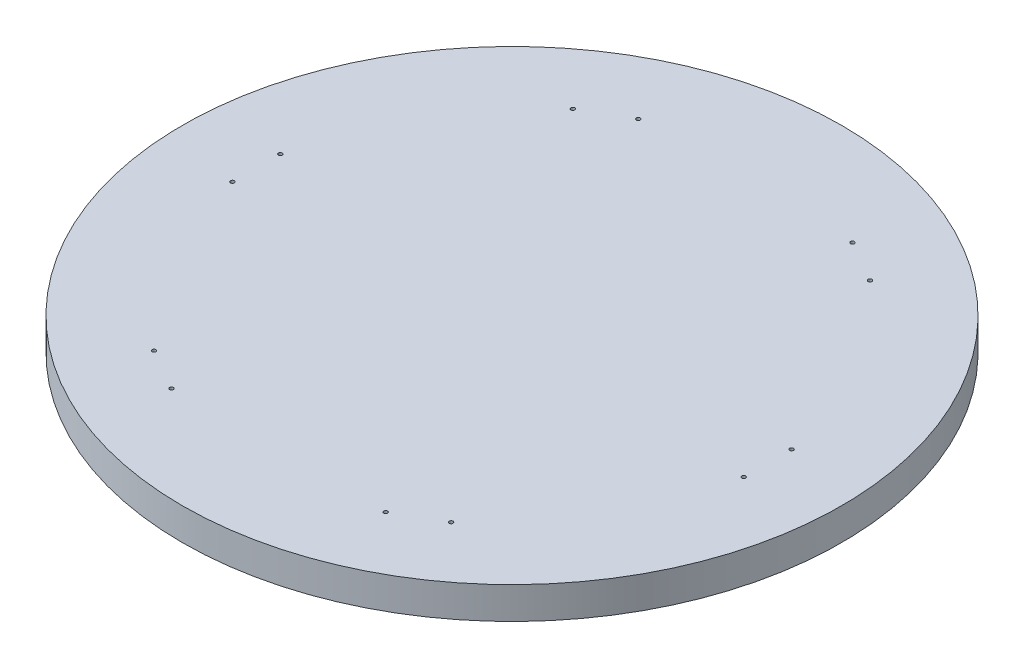
SolidWorks part; units mm, degrees
ref_plane "Front Plane" through (0, 0, 0) normal (0, 0, 1) x (1, 0, 0)
ref_plane "Top Plane" through (0, 0, 0) normal (0, 1, 0) x (1, 0, 0)
ref_plane "Right Plane" through (0, 0, 0) normal (1, 0, 0) x (0, 0, -1)
sketch "Sketch1" plane through (0, 0, 0) normal (0, 1, 0) x (1, 0, 0)
  circle A0 centre (0, 0) radius 261.9375
extrude "Boss-Extrude1" add sketch "Sketch1" along normal blind 25.4
sketch "Sketch6" plane through (0, 0, 0) normal (0, -1, 0) x (1, 0, 0)
  line L0 (203.2, 19.05) -> (203.2, -19.05) construction
  line L1 (215.9, 19.05) -> (215.9, -19.05)
  line L2 (190.5, 19.05) -> (190.5, -19.05)
  line L3 (203.2, -16.5451) -> (201.0307, -17.7976) construction
  line L4 (201.0307, -17.7976) -> (201.0307, -20.3024) construction
  line L5 (201.0307, -20.3024) -> (203.2, -21.5549) construction
  line L6 (203.2, -21.5549) -> (205.3693, -20.3024) construction
  line L7 (205.3693, -20.3024) -> (205.3693, -17.7976) construction
  line L8 (205.3693, -17.7976) -> (203.2, -16.5451) construction
  line L9 (203.2, 22.1294) -> (201.0307, 20.8769) construction
  line L10 (201.0307, 20.8769) -> (201.0307, 18.372) construction
  line L11 (201.0307, 18.372) -> (203.2, 17.1196) construction
  line L12 (203.2, 17.1196) -> (205.3693, 18.372) construction
  line L13 (205.3693, 18.372) -> (205.3693, 20.8769) construction
  line L14 (205.3693, 20.8769) -> (203.2, 22.1294) construction
  line L15 (0, 0) -> (203.2, 0) construction
  line L16 (87.2715, -184.2489) -> (85.1022, -182.9965) construction
  line L17 (85.1022, -182.9965) -> (82.9329, -184.2489) construction
  line L18 (82.9329, -184.2489) -> (82.9329, -186.7538) construction
  line L19 (82.9329, -186.7538) -> (85.1022, -188.0063) construction
  line L20 (85.1022, -188.0063) -> (87.2715, -186.7538) construction
  line L21 (87.2715, -186.7538) -> (87.2715, -184.2489) construction
  line L22 (120.7646, -164.9117) -> (118.5953, -163.6592) construction
  line L23 (118.5953, -163.6592) -> (116.426, -164.9117) construction
  line L24 (116.426, -164.9117) -> (116.426, -167.4166) construction
  line L25 (116.426, -167.4166) -> (118.5953, -168.669) construction
  line L26 (118.5953, -168.669) -> (120.7646, -167.4166) construction
  line L27 (120.7646, -167.4166) -> (120.7646, -164.9117) construction
  line L28 (0, 0) -> (101.6, -175.9764) construction
  line L29 (118.0978, -166.4514) -> (85.1022, -185.5014) construction
  line L30 (124.4478, -177.4499) -> (91.4522, -196.4999)
  line L31 (111.7478, -155.4528) -> (78.7522, -174.5028)
  line L32 (-115.9285, -167.7038) -> (-115.9285, -165.1989) construction
  line L33 (-115.9285, -165.1989) -> (-118.0978, -163.9465) construction
  line L34 (-118.0978, -163.9465) -> (-120.2671, -165.1989) construction
  line L35 (-120.2671, -165.1989) -> (-120.2671, -167.7038) construction
  line L36 (-120.2671, -167.7038) -> (-118.0978, -168.9563) construction
  line L37 (-118.0978, -168.9563) -> (-115.9285, -167.7038) construction
  line L38 (-82.4354, -187.0411) -> (-82.4354, -184.5362) construction
  line L39 (-82.4354, -184.5362) -> (-84.6047, -183.2837) construction
  line L40 (-84.6047, -183.2837) -> (-86.774, -184.5362) construction
  line L41 (-86.774, -184.5362) -> (-86.774, -187.0411) construction
  line L42 (-86.774, -187.0411) -> (-84.6047, -188.2935) construction
  line L43 (-84.6047, -188.2935) -> (-82.4354, -187.0411) construction
  line L44 (0, 0) -> (-101.6, -175.9764) construction
  line L45 (-85.1022, -185.5014) -> (-118.0978, -166.4514) construction
  line L46 (-91.4522, -196.4999) -> (-124.4478, -177.4499)
  line L47 (-78.7522, -174.5028) -> (-111.7478, -155.4528)
  line L48 (-203.2, 16.5451) -> (-201.0307, 17.7976) construction
  line L49 (-201.0307, 17.7976) -> (-201.0307, 20.3024) construction
  line L50 (-201.0307, 20.3024) -> (-203.2, 21.5549) construction
  line L51 (-203.2, 21.5549) -> (-205.3693, 20.3024) construction
  line L52 (-205.3693, 20.3024) -> (-205.3693, 17.7976) construction
  line L53 (-205.3693, 17.7976) -> (-203.2, 16.5451) construction
  line L54 (-203.2, -22.1294) -> (-201.0307, -20.8769) construction
  line L55 (-201.0307, -20.8769) -> (-201.0307, -18.372) construction
  line L56 (-201.0307, -18.372) -> (-203.2, -17.1196) construction
  line L57 (-203.2, -17.1196) -> (-205.3693, -18.372) construction
  line L58 (-205.3693, -18.372) -> (-205.3693, -20.8769) construction
  line L59 (-205.3693, -20.8769) -> (-203.2, -22.1294) construction
  line L60 (0, 0) -> (-203.2, 0) construction
  line L61 (-203.2, -19.05) -> (-203.2, 19.05) construction
  line L62 (-215.9, -19.05) -> (-215.9, 19.05)
  line L63 (-190.5, -19.05) -> (-190.5, 19.05)
  line L64 (-87.2715, 184.2489) -> (-85.1022, 182.9965) construction
  line L65 (-85.1022, 182.9965) -> (-82.9329, 184.2489) construction
  line L66 (-82.9329, 184.2489) -> (-82.9329, 186.7538) construction
  line L67 (-82.9329, 186.7538) -> (-85.1022, 188.0063) construction
  line L68 (-85.1022, 188.0063) -> (-87.2715, 186.7538) construction
  line L69 (-87.2715, 186.7538) -> (-87.2715, 184.2489) construction
  line L70 (-120.7646, 164.9117) -> (-118.5953, 163.6592) construction
  line L71 (-118.5953, 163.6592) -> (-116.426, 164.9117) construction
  line L72 (-116.426, 164.9117) -> (-116.426, 167.4166) construction
  line L73 (-116.426, 167.4166) -> (-118.5953, 168.669) construction
  line L74 (-118.5953, 168.669) -> (-120.7646, 167.4166) construction
  line L75 (-120.7646, 167.4166) -> (-120.7646, 164.9117) construction
  line L76 (0, 0) -> (-101.6, 175.9764) construction
  line L77 (-118.0978, 166.4514) -> (-85.1022, 185.5014) construction
  line L78 (-124.4478, 177.4499) -> (-91.4522, 196.4999)
  line L79 (-111.7478, 155.4528) -> (-78.7522, 174.5028)
  line L80 (115.9285, 167.7038) -> (115.9285, 165.1989) construction
  line L81 (115.9285, 165.1989) -> (118.0978, 163.9465) construction
  line L82 (118.0978, 163.9465) -> (120.2671, 165.1989) construction
  line L83 (120.2671, 165.1989) -> (120.2671, 167.7038) construction
  line L84 (120.2671, 167.7038) -> (118.0978, 168.9563) construction
  line L85 (118.0978, 168.9563) -> (115.9285, 167.7038) construction
  line L86 (82.4354, 187.0411) -> (82.4354, 184.5362) construction
  line L87 (82.4354, 184.5362) -> (84.6047, 183.2837) construction
  line L88 (84.6047, 183.2837) -> (86.774, 184.5362) construction
  line L89 (86.774, 184.5362) -> (86.774, 187.0411) construction
  line L90 (86.774, 187.0411) -> (84.6047, 188.2935) construction
  line L91 (84.6047, 188.2935) -> (82.4354, 187.0411) construction
  line L92 (0, 0) -> (101.6, 175.9764) construction
  line L93 (85.1022, 185.5014) -> (118.0978, 166.4514) construction
  line L94 (91.4522, 196.4999) -> (124.4478, 177.4499)
  line L95 (78.7522, 174.5028) -> (111.7478, 155.4528)
  arc A0 (215.9, 19.05) -> (190.5, 19.05) centre (203.2, 19.05) ccw
  arc A1 (190.5, -19.05) -> (215.9, -19.05) centre (203.2, -19.05) ccw
  circle A2 centre (203.2, -19.05) radius 2.1693 construction
  circle A3 centre (203.2, 19.6245) radius 2.1693 construction
  circle A4 centre (203.2, -19.05) radius 1.524 construction
  circle A5 centre (203.2, 19.6245) radius 1.524 construction
  circle A6 centre (85.1022, -185.5014) radius 2.1693 construction
  circle A7 centre (118.5953, -166.1641) radius 2.1693 construction
  circle A8 centre (85.1022, -185.5014) radius 1.524 construction
  circle A9 centre (118.5953, -166.1641) radius 1.524 construction
  arc A10 (124.4478, -177.4499) -> (111.7478, -155.4528) centre (118.0978, -166.4514) ccw
  arc A11 (78.7522, -174.5028) -> (91.4522, -196.4999) centre (85.1022, -185.5014) ccw
  circle A12 centre (-118.0978, -166.4514) radius 2.1693 construction
  circle A13 centre (-84.6047, -185.7886) radius 2.1693 construction
  circle A14 centre (-118.0978, -166.4514) radius 1.524 construction
  circle A15 centre (-84.6047, -185.7886) radius 1.524 construction
  arc A16 (-91.4522, -196.4999) -> (-78.7522, -174.5028) centre (-85.1022, -185.5014) ccw
  arc A17 (-111.7478, -155.4528) -> (-124.4478, -177.4499) centre (-118.0978, -166.4514) ccw
  circle A18 centre (-203.2, 19.05) radius 2.1693 construction
  circle A19 centre (-203.2, -19.6245) radius 2.1693 construction
  circle A20 centre (-203.2, 19.05) radius 1.524 construction
  circle A21 centre (-203.2, -19.6245) radius 1.524 construction
  arc A22 (-215.9, -19.05) -> (-190.5, -19.05) centre (-203.2, -19.05) ccw
  arc A23 (-190.5, 19.05) -> (-215.9, 19.05) centre (-203.2, 19.05) ccw
  circle A24 centre (-85.1022, 185.5014) radius 2.1693 construction
  circle A25 centre (-118.5953, 166.1641) radius 2.1693 construction
  circle A26 centre (-85.1022, 185.5014) radius 1.524 construction
  circle A27 centre (-118.5953, 166.1641) radius 1.524 construction
  arc A28 (-124.4478, 177.4499) -> (-111.7478, 155.4528) centre (-118.0978, 166.4514) ccw
  arc A29 (-78.7522, 174.5028) -> (-91.4522, 196.4999) centre (-85.1022, 185.5014) ccw
  circle A30 centre (118.0978, 166.4514) radius 2.1693 construction
  circle A31 centre (84.6047, 185.7886) radius 2.1693 construction
  circle A32 centre (118.0978, 166.4514) radius 1.524 construction
  circle A33 centre (84.6047, 185.7886) radius 1.524 construction
  arc A34 (91.4522, 196.4999) -> (78.7522, 174.5028) centre (85.1022, 185.5014) ccw
  arc A35 (111.7478, 155.4528) -> (124.4478, 177.4499) centre (118.0978, 166.4514) ccw
  point P2 (203.2, 0)
  point P32 (101.6, -175.9764)
  point P58 (-101.6, -175.9764)
  point P84 (-203.2, 0)
  point P110 (-101.6, 175.9764)
  point P136 (101.6, 175.9764)
  point P160 (0, 0)
  dimension "D1" = 6
extrude "Cut-Extrude4" cut sketch "Sketch6" against normal blind 12.7
sketch "Sketch9" plane through (0, 0, 0) normal (0, -1, 0) x (1, 0, 0)
  circle A0 centre (0, 0) radius 25.4
extrude "Boss-Extrude2" add sketch "Sketch9" along normal blind 10.16 and the other way through all
sketch "Sketch10" plane through (0, -10.16, 0) normal (0, -1, 0) x (1, 0, 0)
  line L0 (0, -2.032) -> (0, 1.524) construction
  line L1 (-1.344, 1.524) -> (1.344, 1.524)
  line L2 (-2.032, 0) -> (-2.032, 1.524)
  line L3 (-2.032, 1.524) -> (-1.344, 1.524)
  line L4 (2.032, 0) -> (2.032, 1.524)
  line L5 (2.032, 1.524) -> (1.344, 1.524)
  arc A0 (-2.032, 0) -> (2.032, 0) centre (0, 0) ccw
extrude "Cut-Extrude7" cut sketch "Sketch10" against normal blind 19.05
sketch "Sketch11" plane through (0, 0, 0) normal (0, -1, 0) x (1, 0, 0)
  line L0 (0, 0) -> (-11.1642, -177.4492) construction
  line L1 (0, 0) -> (0, -291.8902) construction
  line L2 (0, 0) -> (11.1642, -177.4492) construction
  line L3 (-33.3164, -174.6507) -> (-22.2403, -176.0499) construction
  line L4 (-11.1642, -177.4492) -> (0, -177.4492) construction
  line L5 (0, -177.4492) -> (11.1642, -177.4492) construction
  line L6 (-22.2403, -176.0499) -> (-11.1642, -177.4492) construction
  line L7 (-54.9432, -169.0978) -> (-44.1298, -171.8743) construction
  line L8 (-44.1298, -171.8743) -> (-33.3164, -174.6507) construction
  line L9 (-75.7036, -160.8782) -> (-65.3234, -164.988) construction
  line L10 (-65.3234, -164.988) -> (-54.9432, -169.0978) construction
  line L11 (-95.27, -150.1215) -> (-85.4868, -155.4999) construction
  line L12 (-85.4868, -155.4999) -> (-75.7036, -160.8782) construction
  line L13 (-113.334, -136.9973) -> (-104.302, -143.5594) construction
  line L14 (-104.302, -143.5594) -> (-95.27, -150.1215) construction
  line L15 (-129.6106, -121.7125) -> (-121.4723, -129.3549) construction
  line L16 (-121.4723, -129.3549) -> (-113.334, -136.9973) construction
  line L17 (-143.8432, -104.5082) -> (-136.7269, -113.1103) construction
  line L18 (-136.7269, -113.1103) -> (-129.6106, -121.7125) construction
  line L19 (-155.8073, -85.6558) -> (-149.8253, -95.082) construction
  line L20 (-149.8253, -95.082) -> (-143.8432, -104.5082) construction
  line L21 (-165.3143, -65.4525) -> (-160.5608, -75.5542) construction
  line L22 (-160.5608, -75.5542) -> (-155.8073, -85.6558) construction
  line L23 (-172.2141, -44.2171) -> (-168.7642, -54.8348) construction
  line L24 (-168.7642, -54.8348) -> (-165.3143, -65.4525) construction
  line L25 (-176.398, -22.2842) -> (-174.306, -33.2507) construction
  line L26 (-174.306, -33.2507) -> (-172.2141, -44.2171) construction
  line L27 (-177.8, 0) -> (-177.099, -11.1421) construction
  line L28 (-177.099, -11.1421) -> (-176.398, -22.2842) construction
  line L29 (-176.398, 22.2842) -> (-177.099, 11.1421) construction
  line L30 (-177.099, 11.1421) -> (-177.8, 0) construction
  line L31 (-172.2141, 44.2171) -> (-174.306, 33.2507) construction
  line L32 (-174.306, 33.2507) -> (-176.398, 22.2842) construction
  line L33 (-165.3143, 65.4525) -> (-168.7642, 54.8348) construction
  line L34 (-168.7642, 54.8348) -> (-172.2141, 44.2171) construction
  line L35 (-155.8073, 85.6558) -> (-160.5608, 75.5542) construction
  line L36 (-160.5608, 75.5542) -> (-165.3143, 65.4525) construction
  line L37 (-143.8432, 104.5082) -> (-149.8253, 95.082) construction
  line L38 (-149.8253, 95.082) -> (-155.8073, 85.6558) construction
  line L39 (-129.6106, 121.7125) -> (-136.7269, 113.1103) construction
  line L40 (-136.7269, 113.1103) -> (-143.8432, 104.5082) construction
  line L41 (-113.334, 136.9973) -> (-121.4723, 129.3549) construction
  line L42 (-121.4723, 129.3549) -> (-129.6106, 121.7125) construction
  line L43 (-95.27, 150.1215) -> (-104.302, 143.5594) construction
  line L44 (-104.302, 143.5594) -> (-113.334, 136.9973) construction
  line L45 (-75.7036, 160.8782) -> (-85.4868, 155.4999) construction
  line L46 (-85.4868, 155.4999) -> (-95.27, 150.1215) construction
  line L47 (-54.9432, 169.0978) -> (-65.3234, 164.988) construction
  line L48 (-65.3234, 164.988) -> (-75.7036, 160.8782) construction
  line L49 (-33.3164, 174.6507) -> (-44.1298, 171.8743) construction
  line L50 (-44.1298, 171.8743) -> (-54.9432, 169.0978) construction
  line L51 (-11.1642, 177.4492) -> (-22.2403, 176.0499) construction
  line L52 (-22.2403, 176.0499) -> (-33.3164, 174.6507) construction
  line L53 (11.1642, 177.4492) -> (0, 177.4492) construction
  line L54 (0, 177.4492) -> (-11.1642, 177.4492) construction
  line L55 (33.3164, 174.6507) -> (22.2403, 176.0499) construction
  line L56 (22.2403, 176.0499) -> (11.1642, 177.4492) construction
  line L57 (54.9432, 169.0978) -> (44.1298, 171.8743) construction
  line L58 (44.1298, 171.8743) -> (33.3164, 174.6507) construction
  line L59 (75.7036, 160.8782) -> (65.3234, 164.988) construction
  line L60 (65.3234, 164.988) -> (54.9432, 169.0978) construction
  line L61 (95.27, 150.1215) -> (85.4868, 155.4999) construction
  line L62 (85.4868, 155.4999) -> (75.7036, 160.8782) construction
  line L63 (113.334, 136.9973) -> (104.302, 143.5594) construction
  line L64 (104.302, 143.5594) -> (95.27, 150.1215) construction
  line L65 (129.6106, 121.7125) -> (121.4723, 129.3549) construction
  line L66 (121.4723, 129.3549) -> (113.334, 136.9973) construction
  line L67 (143.8432, 104.5082) -> (136.7269, 113.1103) construction
  line L68 (136.7269, 113.1103) -> (129.6106, 121.7125) construction
  line L69 (155.8073, 85.6558) -> (149.8253, 95.082) construction
  line L70 (149.8253, 95.082) -> (143.8432, 104.5082) construction
  line L71 (165.3143, 65.4525) -> (160.5608, 75.5542) construction
  line L72 (160.5608, 75.5542) -> (155.8073, 85.6558) construction
  line L73 (172.2141, 44.2171) -> (168.7642, 54.8348) construction
  line L74 (168.7642, 54.8348) -> (165.3143, 65.4525) construction
  line L75 (176.398, 22.2842) -> (174.306, 33.2507) construction
  line L76 (174.306, 33.2507) -> (172.2141, 44.2171) construction
  line L77 (177.8, 0) -> (177.099, 11.1421) construction
  line L78 (177.099, 11.1421) -> (176.398, 22.2842) construction
  line L79 (176.398, -22.2842) -> (177.099, -11.1421) construction
  line L80 (177.099, -11.1421) -> (177.8, 0) construction
  line L81 (172.2141, -44.2171) -> (174.306, -33.2507) construction
  line L82 (174.306, -33.2507) -> (176.398, -22.2842) construction
  line L83 (165.3143, -65.4525) -> (168.7642, -54.8348) construction
  line L84 (168.7642, -54.8348) -> (172.2141, -44.2171) construction
  line L85 (155.8073, -85.6558) -> (160.5608, -75.5542) construction
  line L86 (160.5608, -75.5542) -> (165.3143, -65.4525) construction
  line L87 (143.8432, -104.5082) -> (149.8253, -95.082) construction
  line L88 (149.8253, -95.082) -> (155.8073, -85.6558) construction
  line L89 (129.6106, -121.7125) -> (136.7269, -113.1103) construction
  line L90 (136.7269, -113.1103) -> (143.8432, -104.5082) construction
  line L91 (113.334, -136.9973) -> (121.4723, -129.3549) construction
  line L92 (121.4723, -129.3549) -> (129.6106, -121.7125) construction
  line L93 (95.27, -150.1215) -> (104.302, -143.5594) construction
  line L94 (104.302, -143.5594) -> (113.334, -136.9973) construction
  line L95 (75.7036, -160.8782) -> (85.4868, -155.4999) construction
  line L96 (85.4868, -155.4999) -> (95.27, -150.1215) construction
  line L97 (54.9432, -169.0978) -> (65.3234, -164.988) construction
  line L98 (65.3234, -164.988) -> (75.7036, -160.8782) construction
  line L99 (33.3164, -174.6507) -> (44.1298, -171.8743) construction
  line L100 (44.1298, -171.8743) -> (54.9432, -169.0978) construction
  line L101 (11.1642, -177.4492) -> (22.2403, -176.0499) construction
  line L102 (22.2403, -176.0499) -> (33.3164, -174.6507) construction
  circle A0 centre (0, 0) radius 177.8 construction
  arc A1 (0, -177.4492) -> (-11.1201, -176.7495) centre (-5.5821, -177.4492) ccw
  arc A2 (0, -177.4492) -> (11.1201, -176.7495) centre (5.5821, -177.4492) ccw
  arc A3 (-22.2403, -176.0499) -> (-33.185, -173.9621) centre (-27.7783, -175.3503) ccw
  arc A4 (-22.2403, -176.0499) -> (-11.1201, -176.7495) centre (-16.7022, -176.7495) ccw
  arc A5 (-44.1298, -171.8743) -> (-54.7266, -168.4312) centre (-49.5365, -170.4861) ccw
  arc A6 (-44.1298, -171.8743) -> (-33.185, -173.9621) centre (-38.7231, -173.2625) ccw
  arc A7 (-65.3234, -164.988) -> (-75.4051, -160.244) centre (-70.5135, -162.9331) ccw
  arc A8 (-65.3234, -164.988) -> (-54.7266, -168.4312) centre (-60.1333, -167.0429) ccw
  arc A9 (-85.4868, -155.4999) -> (-94.8944, -149.5296) centre (-90.3784, -152.8107) ccw
  arc A10 (-85.4868, -155.4999) -> (-75.4051, -160.244) centre (-80.5952, -158.1891) ccw
  arc A11 (-104.302, -143.5594) -> (-112.8871, -136.4571) centre (-108.818, -140.2783) ccw
  arc A12 (-104.302, -143.5594) -> (-94.8944, -149.5296) centre (-99.786, -146.8404) ccw
  arc A13 (-121.4723, -129.3549) -> (-129.0996, -121.2326) centre (-125.5415, -125.5337) ccw
  arc A14 (-121.4723, -129.3549) -> (-112.8871, -136.4571) centre (-117.4031, -133.1761) ccw
  arc A15 (-136.7269, -113.1103) -> (-143.2761, -104.0962) centre (-140.2851, -108.8093) ccw
  arc A16 (-136.7269, -113.1103) -> (-129.0996, -121.2326) centre (-133.1688, -117.4114) ccw
  arc A17 (-149.8253, -95.082) -> (-155.193, -85.3181) centre (-152.8163, -90.3689) ccw
  arc A18 (-149.8253, -95.082) -> (-143.2761, -104.0962) centre (-146.8342, -99.7951) ccw
  arc A19 (-160.5608, -75.5542) -> (-164.6625, -65.1945) centre (-162.9375, -70.5034) ccw
  arc A20 (-160.5608, -75.5542) -> (-155.193, -85.3181) centre (-158.1841, -80.605) ccw
  arc A21 (-168.7642, -54.8348) -> (-171.5351, -44.0427) centre (-170.4891, -49.5259) ccw
  arc A22 (-168.7642, -54.8348) -> (-164.6625, -65.1945) centre (-167.0392, -60.1437) ccw
  arc A23 (-174.306, -33.2507) -> (-175.7025, -22.1964) centre (-175.352, -27.7675) ccw
  arc A24 (-174.306, -33.2507) -> (-171.5351, -44.0427) centre (-173.2601, -38.7339) ccw
  arc A25 (-177.099, -11.1421) -> (-177.099, 0) centre (-177.4495, -5.5711) ccw
  arc A26 (-177.099, -11.1421) -> (-175.7025, -22.1964) centre (-176.7485, -16.7132) ccw
  arc A27 (-177.099, 11.1421) -> (-175.7025, 22.1964) centre (-176.7485, 16.7132) ccw
  arc A28 (-177.099, 11.1421) -> (-177.099, 0) centre (-177.4495, 5.5711) ccw
  arc A29 (-174.306, 33.2507) -> (-171.5351, 44.0427) centre (-173.2601, 38.7339) ccw
  arc A30 (-174.306, 33.2507) -> (-175.7025, 22.1964) centre (-175.352, 27.7675) ccw
  arc A31 (-168.7642, 54.8348) -> (-164.6625, 65.1945) centre (-167.0392, 60.1437) ccw
  arc A32 (-168.7642, 54.8348) -> (-171.5351, 44.0427) centre (-170.4891, 49.5259) ccw
  arc A33 (-160.5608, 75.5542) -> (-155.193, 85.3181) centre (-158.1841, 80.605) ccw
  arc A34 (-160.5608, 75.5542) -> (-164.6625, 65.1945) centre (-162.9375, 70.5034) ccw
  arc A35 (-149.8253, 95.082) -> (-143.2761, 104.0962) centre (-146.8342, 99.7951) ccw
  arc A36 (-149.8253, 95.082) -> (-155.193, 85.3181) centre (-152.8163, 90.3689) ccw
  arc A37 (-136.7269, 113.1103) -> (-129.0996, 121.2326) centre (-133.1688, 117.4114) ccw
  arc A38 (-136.7269, 113.1103) -> (-143.2761, 104.0962) centre (-140.2851, 108.8093) ccw
  arc A39 (-121.4723, 129.3549) -> (-112.8871, 136.4571) centre (-117.4031, 133.1761) ccw
  arc A40 (-121.4723, 129.3549) -> (-129.0996, 121.2326) centre (-125.5415, 125.5337) ccw
  arc A41 (-104.302, 143.5594) -> (-94.8944, 149.5296) centre (-99.786, 146.8404) ccw
  arc A42 (-104.302, 143.5594) -> (-112.8871, 136.4571) centre (-108.818, 140.2783) ccw
  arc A43 (-85.4868, 155.4999) -> (-75.4051, 160.244) centre (-80.5952, 158.1891) ccw
  arc A44 (-85.4868, 155.4999) -> (-94.8944, 149.5296) centre (-90.3784, 152.8107) ccw
  arc A45 (-65.3234, 164.988) -> (-54.7266, 168.4312) centre (-60.1333, 167.0429) ccw
  arc A46 (-65.3234, 164.988) -> (-75.4051, 160.244) centre (-70.5135, 162.9331) ccw
  arc A47 (-44.1298, 171.8743) -> (-33.185, 173.9621) centre (-38.7231, 173.2625) ccw
  arc A48 (-44.1298, 171.8743) -> (-54.7266, 168.4312) centre (-49.5365, 170.4861) ccw
  arc A49 (-22.2403, 176.0499) -> (-11.1201, 176.7495) centre (-16.7022, 176.7495) ccw
  arc A50 (-22.2403, 176.0499) -> (-33.185, 173.9621) centre (-27.7783, 175.3503) ccw
  arc A51 (0, 177.4492) -> (11.1201, 176.7495) centre (5.5821, 177.4492) ccw
  arc A52 (0, 177.4492) -> (-11.1201, 176.7495) centre (-5.5821, 177.4492) ccw
  arc A53 (22.2403, 176.0499) -> (33.185, 173.9621) centre (27.7783, 175.3503) ccw
  arc A54 (22.2403, 176.0499) -> (11.1201, 176.7495) centre (16.7022, 176.7495) ccw
  arc A55 (44.1298, 171.8743) -> (54.7266, 168.4312) centre (49.5365, 170.4861) ccw
  arc A56 (44.1298, 171.8743) -> (33.185, 173.9621) centre (38.7231, 173.2625) ccw
  arc A57 (65.3234, 164.988) -> (75.4051, 160.244) centre (70.5135, 162.9331) ccw
  arc A58 (65.3234, 164.988) -> (54.7266, 168.4312) centre (60.1333, 167.0429) ccw
  arc A59 (85.4868, 155.4999) -> (94.8944, 149.5296) centre (90.3784, 152.8107) ccw
  arc A60 (85.4868, 155.4999) -> (75.4051, 160.244) centre (80.5952, 158.1891) ccw
  arc A61 (104.302, 143.5594) -> (112.8871, 136.4571) centre (108.818, 140.2783) ccw
  arc A62 (104.302, 143.5594) -> (94.8944, 149.5296) centre (99.786, 146.8404) ccw
  arc A63 (121.4723, 129.3549) -> (129.0996, 121.2326) centre (125.5415, 125.5337) ccw
  arc A64 (121.4723, 129.3549) -> (112.8871, 136.4571) centre (117.4031, 133.1761) ccw
  arc A65 (136.7269, 113.1103) -> (143.2761, 104.0962) centre (140.2851, 108.8093) ccw
  arc A66 (136.7269, 113.1103) -> (129.0996, 121.2326) centre (133.1688, 117.4114) ccw
  arc A67 (149.8253, 95.082) -> (155.193, 85.3181) centre (152.8163, 90.3689) ccw
  arc A68 (149.8253, 95.082) -> (143.2761, 104.0962) centre (146.8342, 99.7951) ccw
  arc A69 (160.5608, 75.5542) -> (164.6625, 65.1945) centre (162.9375, 70.5034) ccw
  arc A70 (160.5608, 75.5542) -> (155.193, 85.3181) centre (158.1841, 80.605) ccw
  arc A71 (168.7642, 54.8348) -> (171.5351, 44.0427) centre (170.4891, 49.5259) ccw
  arc A72 (168.7642, 54.8348) -> (164.6625, 65.1945) centre (167.0392, 60.1437) ccw
  arc A73 (174.306, 33.2507) -> (175.7025, 22.1964) centre (175.352, 27.7675) ccw
  arc A74 (174.306, 33.2507) -> (171.5351, 44.0427) centre (173.2601, 38.7339) ccw
  arc A75 (177.099, 11.1421) -> (177.099, 0) centre (177.4495, 5.5711) ccw
  arc A76 (177.099, 11.1421) -> (175.7025, 22.1964) centre (176.7485, 16.7132) ccw
  arc A77 (177.099, -11.1421) -> (175.7025, -22.1964) centre (176.7485, -16.7132) ccw
  arc A78 (177.099, -11.1421) -> (177.099, 0) centre (177.4495, -5.5711) ccw
  arc A79 (174.306, -33.2507) -> (171.5351, -44.0427) centre (173.2601, -38.7339) ccw
  arc A80 (174.306, -33.2507) -> (175.7025, -22.1964) centre (175.352, -27.7675) ccw
  arc A81 (168.7642, -54.8348) -> (164.6625, -65.1945) centre (167.0392, -60.1437) ccw
  arc A82 (168.7642, -54.8348) -> (171.5351, -44.0427) centre (170.4891, -49.5259) ccw
  arc A83 (160.5608, -75.5542) -> (155.193, -85.3181) centre (158.1841, -80.605) ccw
  arc A84 (160.5608, -75.5542) -> (164.6625, -65.1945) centre (162.9375, -70.5034) ccw
  arc A85 (149.8253, -95.082) -> (143.2761, -104.0962) centre (146.8342, -99.7951) ccw
  arc A86 (149.8253, -95.082) -> (155.193, -85.3181) centre (152.8163, -90.3689) ccw
  arc A87 (136.7269, -113.1103) -> (129.0996, -121.2326) centre (133.1688, -117.4114) ccw
  arc A88 (136.7269, -113.1103) -> (143.2761, -104.0962) centre (140.2851, -108.8093) ccw
  arc A89 (121.4723, -129.3549) -> (112.8871, -136.4571) centre (117.4031, -133.1761) ccw
  arc A90 (121.4723, -129.3549) -> (129.0996, -121.2326) centre (125.5415, -125.5337) ccw
  arc A91 (104.302, -143.5594) -> (94.8944, -149.5296) centre (99.786, -146.8404) ccw
  arc A92 (104.302, -143.5594) -> (112.8871, -136.4571) centre (108.818, -140.2783) ccw
  arc A93 (85.4868, -155.4999) -> (75.4051, -160.244) centre (80.5952, -158.1891) ccw
  arc A94 (85.4868, -155.4999) -> (94.8944, -149.5296) centre (90.3784, -152.8107) ccw
  arc A95 (65.3234, -164.988) -> (54.7266, -168.4312) centre (60.1333, -167.0429) ccw
  arc A96 (65.3234, -164.988) -> (75.4051, -160.244) centre (70.5135, -162.9331) ccw
  arc A97 (44.1298, -171.8743) -> (33.185, -173.9621) centre (38.7231, -173.2625) ccw
  arc A98 (44.1298, -171.8743) -> (54.7266, -168.4312) centre (49.5365, -170.4861) ccw
  arc A99 (22.2403, -176.0499) -> (11.1201, -176.7495) centre (16.7022, -176.7495) ccw
  arc A100 (22.2403, -176.0499) -> (33.185, -173.9621) centre (27.7783, -175.3503) ccw
  circle A101 centre (0, 0) radius 27.7675
  point P356 (0, 0)
  dimension "D1" = 50
extrude "Cut-Extrude9" cut sketch "Sketch11" against normal blind 6.35
sketch "Sketch12" plane through (0, 12.7, 0) normal (0, -1, 0) x (1, 0, 0)
  line L0 (203.2, 19.05) -> (203.2, -19.05) construction
  line L1 (215.9, 19.05) -> (215.9, -19.05) construction
  line L2 (190.5, 19.05) -> (190.5, -19.05) construction
  line L3 (203.2, -16.5451) -> (201.0307, -17.7975) construction
  line L4 (201.0307, -17.7975) -> (201.0307, -20.3024) construction
  line L5 (201.0307, -20.3024) -> (203.2, -21.5549) construction
  line L6 (203.2, -21.5549) -> (205.3693, -20.3024) construction
  line L7 (205.3693, -20.3024) -> (205.3693, -17.7975) construction
  line L8 (205.3693, -17.7975) -> (203.2, -16.5451) construction
  line L9 (203.2, 21.5549) -> (201.0307, 20.3025) construction
  line L10 (201.0307, 20.3025) -> (201.0307, 17.7976) construction
  line L11 (201.0307, 17.7976) -> (203.2, 16.5451) construction
  line L12 (203.2, 16.5451) -> (205.3693, 17.7976) construction
  line L13 (205.3693, 17.7976) -> (205.3693, 20.3025) construction
  line L14 (205.3693, 20.3025) -> (203.2, 21.5549) construction
  line L15 (190.5, -19.05) -> (203.2, -19.05) construction
  line L16 (87.2715, -184.2489) -> (85.1022, -182.9965) construction
  line L17 (85.1022, -182.9965) -> (82.9329, -184.2489) construction
  line L18 (82.9329, -184.2489) -> (82.9329, -186.7538) construction
  line L19 (82.9329, -186.7538) -> (85.1022, -188.0062) construction
  line L20 (85.1022, -188.0062) -> (87.2715, -186.7538) construction
  line L21 (87.2715, -186.7538) -> (87.2715, -184.2489) construction
  line L22 (120.2671, -165.1989) -> (118.0978, -163.9465) construction
  line L23 (118.0978, -163.9465) -> (115.9285, -165.1989) construction
  line L24 (115.9285, -165.1989) -> (115.9285, -167.7038) construction
  line L25 (115.9285, -167.7038) -> (118.0978, -168.9562) construction
  line L26 (118.0978, -168.9562) -> (120.2671, -167.7038) construction
  line L27 (120.2671, -167.7038) -> (120.2671, -165.1989) construction
  line L28 (78.7522, -174.5028) -> (85.1022, -185.5014) construction
  line L29 (118.0978, -166.4514) -> (85.1022, -185.5014) construction
  line L30 (124.4478, -177.4499) -> (91.4522, -196.4999) construction
  line L31 (111.7478, -155.4528) -> (78.7522, -174.5028) construction
  line L32 (-115.9285, -167.7038) -> (-115.9285, -165.1989) construction
  line L33 (-115.9285, -165.1989) -> (-118.0978, -163.9465) construction
  line L34 (-118.0978, -163.9465) -> (-120.2671, -165.1989) construction
  line L35 (-120.2671, -165.1989) -> (-120.2671, -167.7038) construction
  line L36 (-120.2671, -167.7038) -> (-118.0978, -168.9563) construction
  line L37 (-118.0978, -168.9563) -> (-115.9285, -167.7038) construction
  line L38 (-82.9329, -186.7538) -> (-82.9329, -184.2489) construction
  line L39 (-82.9329, -184.2489) -> (-85.1022, -182.9965) construction
  line L40 (-85.1022, -182.9965) -> (-87.2715, -184.2489) construction
  line L41 (-87.2715, -184.2489) -> (-87.2715, -186.7538) construction
  line L42 (-87.2715, -186.7538) -> (-85.1022, -188.0063) construction
  line L43 (-85.1022, -188.0063) -> (-82.9329, -186.7538) construction
  line L44 (-111.7478, -155.4528) -> (-118.0978, -166.4514) construction
  line L45 (-85.1022, -185.5014) -> (-118.0978, -166.4514) construction
  line L46 (-91.4522, -196.4999) -> (-124.4478, -177.4499) construction
  line L47 (-78.7522, -174.5028) -> (-111.7478, -155.4528) construction
  line L48 (-203.2, 16.5451) -> (-201.0307, 17.7975) construction
  line L49 (-201.0307, 17.7975) -> (-201.0307, 20.3024) construction
  line L50 (-201.0307, 20.3024) -> (-203.2, 21.5549) construction
  line L51 (-203.2, 21.5549) -> (-205.3693, 20.3024) construction
  line L52 (-205.3693, 20.3024) -> (-205.3693, 17.7975) construction
  line L53 (-205.3693, 17.7975) -> (-203.2, 16.5451) construction
  line L54 (-203.2, -21.5549) -> (-201.0307, -20.3025) construction
  line L55 (-201.0307, -20.3025) -> (-201.0307, -17.7976) construction
  line L56 (-201.0307, -17.7976) -> (-203.2, -16.5451) construction
  line L57 (-203.2, -16.5451) -> (-205.3693, -17.7976) construction
  line L58 (-205.3693, -17.7976) -> (-205.3693, -20.3025) construction
  line L59 (-205.3693, -20.3025) -> (-203.2, -21.5549) construction
  line L60 (-190.5, 19.05) -> (-203.2, 19.05) construction
  line L61 (-203.2, -19.05) -> (-203.2, 19.05) construction
  line L62 (-215.9, -19.05) -> (-215.9, 19.05) construction
  line L63 (-190.5, -19.05) -> (-190.5, 19.05) construction
  line L64 (-87.2715, 184.2489) -> (-85.1022, 182.9965) construction
  line L65 (-85.1022, 182.9965) -> (-82.9329, 184.2489) construction
  line L66 (-82.9329, 184.2489) -> (-82.9329, 186.7538) construction
  line L67 (-82.9329, 186.7538) -> (-85.1022, 188.0062) construction
  line L68 (-85.1022, 188.0062) -> (-87.2715, 186.7538) construction
  line L69 (-87.2715, 186.7538) -> (-87.2715, 184.2489) construction
  line L70 (-120.2671, 165.1989) -> (-118.0978, 163.9465) construction
  line L71 (-118.0978, 163.9465) -> (-115.9285, 165.1989) construction
  line L72 (-115.9285, 165.1989) -> (-115.9285, 167.7038) construction
  line L73 (-115.9285, 167.7038) -> (-118.0978, 168.9562) construction
  line L74 (-118.0978, 168.9562) -> (-120.2671, 167.7038) construction
  line L75 (-120.2671, 167.7038) -> (-120.2671, 165.1989) construction
  line L76 (-78.7522, 174.5028) -> (-85.1022, 185.5014) construction
  line L77 (-118.0978, 166.4514) -> (-85.1022, 185.5014) construction
  line L78 (-124.4478, 177.4499) -> (-91.4522, 196.4999) construction
  line L79 (-111.7478, 155.4528) -> (-78.7522, 174.5028) construction
  line L80 (115.9285, 167.7038) -> (115.9285, 165.1989) construction
  line L81 (115.9285, 165.1989) -> (118.0978, 163.9465) construction
  line L82 (118.0978, 163.9465) -> (120.2671, 165.1989) construction
  line L83 (120.2671, 165.1989) -> (120.2671, 167.7038) construction
  line L84 (120.2671, 167.7038) -> (118.0978, 168.9563) construction
  line L85 (118.0978, 168.9563) -> (115.9285, 167.7038) construction
  line L86 (82.9329, 186.7538) -> (82.9329, 184.2489) construction
  line L87 (82.9329, 184.2489) -> (85.1022, 182.9965) construction
  line L88 (85.1022, 182.9965) -> (87.2715, 184.2489) construction
  line L89 (87.2715, 184.2489) -> (87.2715, 186.7538) construction
  line L90 (87.2715, 186.7538) -> (85.1022, 188.0063) construction
  line L91 (85.1022, 188.0063) -> (82.9329, 186.7538) construction
  line L92 (111.7478, 155.4528) -> (118.0978, 166.4514) construction
  line L93 (85.1022, 185.5014) -> (118.0978, 166.4514) construction
  line L94 (91.4522, 196.4999) -> (124.4478, 177.4499) construction
  line L95 (78.7522, 174.5028) -> (111.7478, 155.4528) construction
  line L96 (0, 0) -> (-101.6, 175.9764) construction
  arc A0 (215.9, 19.05) -> (190.5, 19.05) centre (203.2, 19.05) ccw construction
  arc A1 (190.5, -19.05) -> (215.9, -19.05) centre (203.2, -19.05) ccw construction
  circle A2 centre (203.2, -19.05) radius 2.1693 construction
  circle A3 centre (203.2, 19.05) radius 2.1693 construction
  circle A4 centre (203.2, -19.05) radius 1.524
  circle A5 centre (203.2, 19.05) radius 1.524
  circle A6 centre (85.1022, -185.5014) radius 1.524
  circle A7 centre (118.0978, -166.4514) radius 1.524
  circle A8 centre (85.1022, -185.5014) radius 2.1693 construction
  circle A9 centre (118.0978, -166.4514) radius 2.1693 construction
  arc A10 (124.4478, -177.4499) -> (111.7478, -155.4528) centre (118.0978, -166.4514) ccw construction
  arc A11 (78.7522, -174.5028) -> (91.4522, -196.4999) centre (85.1022, -185.5014) ccw construction
  circle A12 centre (-118.0978, -166.4514) radius 1.524
  circle A13 centre (-85.1022, -185.5014) radius 1.524
  circle A14 centre (-118.0978, -166.4514) radius 2.1693 construction
  circle A15 centre (-85.1022, -185.5014) radius 2.1693 construction
  arc A16 (-91.4522, -196.4999) -> (-78.7522, -174.5028) centre (-85.1022, -185.5014) ccw construction
  arc A17 (-111.7478, -155.4528) -> (-124.4478, -177.4499) centre (-118.0978, -166.4514) ccw construction
  circle A18 centre (-203.2, 19.05) radius 1.524
  circle A19 centre (-203.2, -19.05) radius 1.524
  circle A20 centre (-203.2, 19.05) radius 2.1693 construction
  circle A21 centre (-203.2, -19.05) radius 2.1693 construction
  arc A22 (-215.9, -19.05) -> (-190.5, -19.05) centre (-203.2, -19.05) ccw construction
  arc A23 (-190.5, 19.05) -> (-215.9, 19.05) centre (-203.2, 19.05) ccw construction
  circle A24 centre (-85.1022, 185.5014) radius 1.524
  circle A25 centre (-118.0978, 166.4514) radius 1.524
  circle A26 centre (-85.1022, 185.5014) radius 2.1693 construction
  circle A27 centre (-118.0978, 166.4514) radius 2.1693 construction
  arc A28 (-124.4478, 177.4499) -> (-111.7478, 155.4528) centre (-118.0978, 166.4514) ccw construction
  arc A29 (-78.7522, 174.5028) -> (-91.4522, 196.4999) centre (-85.1022, 185.5014) ccw construction
  circle A30 centre (118.0978, 166.4514) radius 1.524
  circle A31 centre (85.1022, 185.5014) radius 1.524
  circle A32 centre (118.0978, 166.4514) radius 2.1693 construction
  circle A33 centre (85.1022, 185.5014) radius 2.1693 construction
  arc A34 (91.4522, 196.4999) -> (78.7522, 174.5028) centre (85.1022, 185.5014) ccw construction
  arc A35 (111.7478, 155.4528) -> (124.4478, 177.4499) centre (118.0978, 166.4514) ccw construction
  point P2 (203.2, 0)
  point P29 (101.6, -175.9764)
  point P56 (-101.6, -175.9764)
  point P83 (-203.2, 0)
  point P110 (-101.6, 175.9764)
  point P137 (101.6, 175.9764)
  point P162 (0, 0)
extrude "Cut-Extrude10" cut sketch "Sketch12" against normal through all
sketch "Sketch13" plane through (0, 0, 0) normal (0, -1, 0) x (1, 0, 0)
  line L3 (-33.3164, -174.6507) -> (-22.2403, -176.0499) construction
  line L4 (-11.1642, -177.4492) -> (0, -177.4492) construction
  line L5 (0, -177.4492) -> (11.1642, -177.4492) construction
  line L6 (-22.2403, -176.0499) -> (-11.1642, -177.4492) construction
  line L7 (-54.9432, -169.0978) -> (-44.1298, -171.8743) construction
  line L8 (-44.1298, -171.8743) -> (-33.3164, -174.6507) construction
  line L9 (-75.7036, -160.8782) -> (-65.3234, -164.988) construction
  line L10 (-65.3234, -164.988) -> (-54.9432, -169.0978) construction
  line L11 (-95.27, -150.1215) -> (-85.4868, -155.4999) construction
  line L12 (-85.4868, -155.4999) -> (-75.7036, -160.8782) construction
  line L13 (-113.334, -136.9973) -> (-104.302, -143.5594) construction
  line L14 (-104.302, -143.5594) -> (-95.27, -150.1215) construction
  line L15 (-129.6106, -121.7125) -> (-121.4723, -129.3549) construction
  line L16 (-121.4723, -129.3549) -> (-113.334, -136.9973) construction
  line L17 (-143.8432, -104.5082) -> (-136.7269, -113.1103) construction
  line L18 (-136.7269, -113.1103) -> (-129.6106, -121.7125) construction
  line L19 (-155.8073, -85.6558) -> (-149.8253, -95.082) construction
  line L20 (-149.8253, -95.082) -> (-143.8432, -104.5082) construction
  line L21 (-165.3143, -65.4525) -> (-160.5608, -75.5542) construction
  line L22 (-160.5608, -75.5542) -> (-155.8073, -85.6558) construction
  line L23 (-172.2141, -44.2171) -> (-168.7642, -54.8348) construction
  line L24 (-168.7642, -54.8348) -> (-165.3143, -65.4525) construction
  line L25 (-176.398, -22.2842) -> (-174.306, -33.2507) construction
  line L26 (-174.306, -33.2507) -> (-172.2141, -44.2171) construction
  line L45 (-75.7036, 160.8782) -> (-85.4868, 155.4999) construction
  line L46 (-85.4868, 155.4999) -> (-95.27, 150.1215) construction
  line L47 (-54.9432, 169.0978) -> (-65.3234, 164.988) construction
  line L48 (-65.3234, 164.988) -> (-75.7036, 160.8782) construction
  line L49 (-33.3164, 174.6507) -> (-44.1298, 171.8743) construction
  line L50 (-44.1298, 171.8743) -> (-54.9432, 169.0978) construction
  line L51 (-11.1642, 177.4492) -> (-22.2403, 176.0499) construction
  line L52 (-22.2403, 176.0499) -> (-33.3164, 174.6507) construction
  line L53 (11.1642, 177.4492) -> (0, 177.4492) construction
  line L54 (0, 177.4492) -> (-11.1642, 177.4492) construction
  line L55 (33.3164, 174.6507) -> (22.2403, 176.0499) construction
  line L56 (22.2403, 176.0499) -> (11.1642, 177.4492) construction
  line L57 (54.9432, 169.0978) -> (44.1298, 171.8743) construction
  line L58 (44.1298, 171.8743) -> (33.3164, 174.6507) construction
  line L59 (75.7036, 160.8782) -> (65.3234, 164.988) construction
  line L60 (65.3234, 164.988) -> (54.9432, 169.0978) construction
  line L61 (95.27, 150.1215) -> (85.4868, 155.4999) construction
  line L62 (85.4868, 155.4999) -> (75.7036, 160.8782) construction
  line L63 (113.334, 136.9973) -> (104.302, 143.5594) construction
  line L64 (104.302, 143.5594) -> (95.27, 150.1215) construction
  line L65 (129.6106, 121.7125) -> (121.4723, 129.3549) construction
  line L66 (121.4723, 129.3549) -> (113.334, 136.9973) construction
  line L67 (143.8432, 104.5082) -> (136.7269, 113.1103) construction
  line L68 (136.7269, 113.1103) -> (129.6106, 121.7125) construction
  line L69 (155.8073, 85.6558) -> (149.8253, 95.082) construction
  line L70 (149.8253, 95.082) -> (143.8432, 104.5082) construction
  line L71 (165.3143, 65.4525) -> (160.5608, 75.5542) construction
  line L72 (160.5608, 75.5542) -> (155.8073, 85.6558) construction
  line L73 (172.2141, 44.2171) -> (168.7642, 54.8348) construction
  line L74 (168.7642, 54.8348) -> (165.3143, 65.4525) construction
  line L75 (176.398, 22.2842) -> (174.306, 33.2507) construction
  line L76 (174.306, 33.2507) -> (172.2141, 44.2171) construction
  line L77 (177.8, 0) -> (177.099, 11.1421) construction
  line L78 (177.099, 11.1421) -> (176.398, 22.2842) construction
  line L79 (176.398, -22.2842) -> (177.099, -11.1421) construction
  line L80 (177.099, -11.1421) -> (177.8, 0) construction
  line L81 (172.2141, -44.2171) -> (174.306, -33.2507) construction
  line L82 (174.306, -33.2507) -> (176.398, -22.2842) construction
  line L83 (165.3143, -65.4525) -> (168.7642, -54.8348) construction
  line L84 (168.7642, -54.8348) -> (172.2141, -44.2171) construction
  line L85 (155.8073, -85.6558) -> (160.5608, -75.5542) construction
  line L86 (160.5608, -75.5542) -> (165.3143, -65.4525) construction
  line L87 (143.8432, -104.5082) -> (149.8253, -95.082) construction
  line L88 (149.8253, -95.082) -> (155.8073, -85.6558) construction
  line L89 (129.6106, -121.7125) -> (136.7269, -113.1103) construction
  line L90 (136.7269, -113.1103) -> (143.8432, -104.5082) construction
  line L91 (113.334, -136.9973) -> (121.4723, -129.3549) construction
  line L92 (121.4723, -129.3549) -> (129.6106, -121.7125) construction
  line L93 (95.27, -150.1215) -> (104.302, -143.5594) construction
  line L94 (104.302, -143.5594) -> (113.334, -136.9973) construction
  line L95 (75.7036, -160.8782) -> (85.4868, -155.4999) construction
  line L96 (85.4868, -155.4999) -> (95.27, -150.1215) construction
  line L97 (54.9432, -169.0978) -> (65.3234, -164.988) construction
  line L98 (65.3234, -164.988) -> (75.7036, -160.8782) construction
  line L99 (33.3164, -174.6507) -> (44.1298, -171.8743) construction
  line L100 (44.1298, -171.8743) -> (54.9432, -169.0978) construction
  line L101 (11.1642, -177.4492) -> (22.2403, -176.0499) construction
  line L102 (22.2403, -176.0499) -> (33.3164, -174.6507) construction
  arc A1 (0, -177.4492) -> (-11.1201, -176.7495) centre (-5.5821, -177.4492) ccw
  arc A2 (0, -177.4492) -> (11.1201, -176.7495) centre (5.5821, -177.4492) ccw
  arc A3 (-22.2403, -176.0499) -> (-33.185, -173.9621) centre (-27.7783, -175.3503) ccw
  arc A4 (-22.2403, -176.0499) -> (-11.1201, -176.7495) centre (-16.7022, -176.7495) ccw
  arc A5 (-44.1298, -171.8743) -> (-54.7266, -168.4312) centre (-49.5365, -170.4861) ccw
  arc A6 (-44.1298, -171.8743) -> (-33.185, -173.9621) centre (-38.7231, -173.2625) ccw
  arc A7 (-65.3234, -164.988) -> (-75.4051, -160.244) centre (-70.5135, -162.9331) ccw
  arc A8 (-65.3234, -164.988) -> (-54.7266, -168.4312) centre (-60.1333, -167.0429) ccw
  arc A9 (-85.4868, -155.4999) -> (-94.8944, -149.5296) centre (-90.3784, -152.8107) ccw
  arc A10 (-85.4868, -155.4999) -> (-75.4051, -160.244) centre (-80.5952, -158.1891) ccw
  arc A11 (-104.302, -143.5594) -> (-112.8871, -136.4571) centre (-108.818, -140.2783) ccw
  arc A12 (-104.302, -143.5594) -> (-94.8944, -149.5296) centre (-99.786, -146.8404) ccw
  arc A13 (-121.4723, -129.3549) -> (-129.0996, -121.2326) centre (-125.5415, -125.5337) ccw
  arc A14 (-121.4723, -129.3549) -> (-112.8871, -136.4571) centre (-117.4031, -133.1761) ccw
  arc A15 (-136.7269, -113.1103) -> (-143.2761, -104.0962) centre (-140.2851, -108.8093) ccw
  arc A16 (-136.7269, -113.1103) -> (-129.0996, -121.2326) centre (-133.1688, -117.4114) ccw
  arc A17 (-149.8253, -95.082) -> (-155.193, -85.3181) centre (-152.8163, -90.3689) ccw
  arc A18 (-149.8253, -95.082) -> (-143.2761, -104.0962) centre (-146.8342, -99.7951) ccw
  arc A19 (-160.5608, -75.5542) -> (-164.6625, -65.1945) centre (-162.9375, -70.5034) ccw
  arc A20 (-160.5608, -75.5542) -> (-155.193, -85.3181) centre (-158.1841, -80.605) ccw
  arc A21 (-168.7642, -54.8348) -> (-171.5351, -44.0427) centre (-170.4891, -49.5259) ccw
  arc A22 (-168.7642, -54.8348) -> (-164.6625, -65.1945) centre (-167.0392, -60.1437) ccw
  arc A23 (-174.306, -33.2507) -> (-175.7025, -22.1964) centre (-175.352, -27.7675) ccw
  arc A24 (-174.306, -33.2507) -> (-171.5351, -44.0427) centre (-173.2601, -38.7339) ccw
  arc A25 (-177.099, -11.1421) -> (-177.099, 0) centre (-177.4495, -5.5711) ccw
  arc A26 (-177.099, -11.1421) -> (-175.7025, -22.1964) centre (-176.7485, -16.7132) ccw
  arc A27 (-177.099, 11.1421) -> (-175.7025, 22.1964) centre (-176.7485, 16.7132) ccw
  arc A28 (-177.099, 11.1421) -> (-177.099, 0) centre (-177.4495, 5.5711) ccw
  arc A29 (-174.306, 33.2507) -> (-171.5351, 44.0427) centre (-173.2601, 38.7339) ccw
  arc A30 (-174.306, 33.2507) -> (-175.7025, 22.1964) centre (-175.352, 27.7675) ccw
  arc A31 (-168.7642, 54.8348) -> (-164.6625, 65.1945) centre (-167.0392, 60.1437) ccw
  arc A32 (-168.7642, 54.8348) -> (-171.5351, 44.0427) centre (-170.4891, 49.5259) ccw
  arc A33 (-160.5608, 75.5542) -> (-155.193, 85.3181) centre (-158.1841, 80.605) ccw
  arc A34 (-160.5608, 75.5542) -> (-164.6625, 65.1945) centre (-162.9375, 70.5034) ccw
  arc A35 (-149.8253, 95.082) -> (-143.2761, 104.0962) centre (-146.8342, 99.7951) ccw
  arc A36 (-149.8253, 95.082) -> (-155.193, 85.3181) centre (-152.8163, 90.3689) ccw
  arc A37 (-136.7269, 113.1103) -> (-129.0996, 121.2326) centre (-133.1688, 117.4114) ccw
  arc A38 (-136.7269, 113.1103) -> (-143.2761, 104.0962) centre (-140.2851, 108.8093) ccw
  arc A39 (-121.4723, 129.3549) -> (-112.8871, 136.4571) centre (-117.4031, 133.1761) ccw
  arc A40 (-121.4723, 129.3549) -> (-129.0996, 121.2326) centre (-125.5415, 125.5337) ccw
  arc A41 (-104.302, 143.5594) -> (-94.8944, 149.5296) centre (-99.786, 146.8404) ccw
  arc A42 (-104.302, 143.5594) -> (-112.8871, 136.4571) centre (-108.818, 140.2783) ccw
  arc A43 (-85.4868, 155.4999) -> (-75.4051, 160.244) centre (-80.5952, 158.1891) ccw
  arc A44 (-85.4868, 155.4999) -> (-94.8944, 149.5296) centre (-90.3784, 152.8107) ccw
  arc A45 (-65.3234, 164.988) -> (-54.7266, 168.4312) centre (-60.1333, 167.0429) ccw
  arc A46 (-65.3234, 164.988) -> (-75.4051, 160.244) centre (-70.5135, 162.9331) ccw
  arc A47 (-44.1298, 171.8743) -> (-33.185, 173.9621) centre (-38.7231, 173.2625) ccw
  arc A48 (-44.1298, 171.8743) -> (-54.7266, 168.4312) centre (-49.5365, 170.4861) ccw
  arc A49 (-22.2403, 176.0499) -> (-11.1201, 176.7495) centre (-16.7022, 176.7495) ccw
  arc A50 (-22.2403, 176.0499) -> (-33.185, 173.9621) centre (-27.7783, 175.3503) ccw
  arc A51 (0, 177.4492) -> (11.1201, 176.7495) centre (5.5821, 177.4492) ccw
  arc A52 (0, 177.4492) -> (-11.1201, 176.7495) centre (-5.5821, 177.4492) ccw
  arc A53 (22.2403, 176.0499) -> (33.185, 173.9621) centre (27.7783, 175.3503) ccw
  arc A54 (22.2403, 176.0499) -> (11.1201, 176.7495) centre (16.7022, 176.7495) ccw
  arc A55 (44.1298, 171.8743) -> (54.7266, 168.4312) centre (49.5365, 170.4861) ccw
  arc A56 (44.1298, 171.8743) -> (33.185, 173.9621) centre (38.7231, 173.2625) ccw
  arc A57 (65.3234, 164.988) -> (75.4051, 160.244) centre (70.5135, 162.9331) ccw
  arc A58 (65.3234, 164.988) -> (54.7266, 168.4312) centre (60.1333, 167.0429) ccw
  arc A59 (85.4868, 155.4999) -> (94.8944, 149.5296) centre (90.3784, 152.8107) ccw
  arc A60 (85.4868, 155.4999) -> (75.4051, 160.244) centre (80.5952, 158.1891) ccw
  arc A61 (104.302, 143.5594) -> (112.8871, 136.4571) centre (108.818, 140.2783) ccw
  arc A62 (104.302, 143.5594) -> (94.8944, 149.5296) centre (99.786, 146.8404) ccw
  arc A63 (121.4723, 129.3549) -> (129.0996, 121.2326) centre (125.5415, 125.5337) ccw
  arc A64 (121.4723, 129.3549) -> (112.8871, 136.4571) centre (117.4031, 133.1761) ccw
  arc A65 (136.7269, 113.1103) -> (143.2761, 104.0962) centre (140.2851, 108.8093) ccw
  arc A66 (136.7269, 113.1103) -> (129.0996, 121.2326) centre (133.1688, 117.4114) ccw
  arc A67 (149.8253, 95.082) -> (155.193, 85.3181) centre (152.8163, 90.3689) ccw
  arc A68 (149.8253, 95.082) -> (143.2761, 104.0962) centre (146.8342, 99.7951) ccw
  arc A69 (160.5608, 75.5542) -> (164.6625, 65.1945) centre (162.9375, 70.5034) ccw
  arc A70 (160.5608, 75.5542) -> (155.193, 85.3181) centre (158.1841, 80.605) ccw
  arc A71 (168.7642, 54.8348) -> (171.5351, 44.0427) centre (170.4891, 49.5259) ccw
  arc A72 (168.7642, 54.8348) -> (164.6625, 65.1945) centre (167.0392, 60.1437) ccw
  arc A73 (174.306, 33.2507) -> (175.7025, 22.1964) centre (175.352, 27.7675) ccw
  arc A74 (174.306, 33.2507) -> (171.5351, 44.0427) centre (173.2601, 38.7339) ccw
  arc A75 (177.099, 11.1421) -> (177.099, 0) centre (177.4495, 5.5711) ccw
  arc A76 (177.099, 11.1421) -> (175.7025, 22.1964) centre (176.7485, 16.7132) ccw
  arc A77 (177.099, -11.1421) -> (175.7025, -22.1964) centre (176.7485, -16.7132) ccw
  arc A78 (177.099, -11.1421) -> (177.099, 0) centre (177.4495, -5.5711) ccw
  arc A79 (174.306, -33.2507) -> (171.5351, -44.0427) centre (173.2601, -38.7339) ccw
  arc A80 (174.306, -33.2507) -> (175.7025, -22.1964) centre (175.352, -27.7675) ccw
  arc A81 (168.7642, -54.8348) -> (164.6625, -65.1945) centre (167.0392, -60.1437) ccw
  arc A82 (168.7642, -54.8348) -> (171.5351, -44.0427) centre (170.4891, -49.5259) ccw
  arc A83 (160.5608, -75.5542) -> (155.193, -85.3181) centre (158.1841, -80.605) ccw
  arc A84 (160.5608, -75.5542) -> (164.6625, -65.1945) centre (162.9375, -70.5034) ccw
  arc A85 (149.8253, -95.082) -> (143.2761, -104.0962) centre (146.8342, -99.7951) ccw
  arc A86 (149.8253, -95.082) -> (155.193, -85.3181) centre (152.8163, -90.3689) ccw
  arc A87 (136.7269, -113.1103) -> (129.0996, -121.2326) centre (133.1688, -117.4114) ccw
  arc A88 (136.7269, -113.1103) -> (143.2761, -104.0962) centre (140.2851, -108.8093) ccw
  arc A89 (121.4723, -129.3549) -> (112.8871, -136.4571) centre (117.4031, -133.1761) ccw
  arc A90 (121.4723, -129.3549) -> (129.0996, -121.2326) centre (125.5415, -125.5337) ccw
  arc A91 (104.302, -143.5594) -> (94.8944, -149.5296) centre (99.786, -146.8404) ccw
  arc A92 (104.302, -143.5594) -> (112.8871, -136.4571) centre (108.818, -140.2783) ccw
  arc A93 (85.4868, -155.4999) -> (75.4051, -160.244) centre (80.5952, -158.1891) ccw
  arc A94 (85.4868, -155.4999) -> (94.8944, -149.5296) centre (90.3784, -152.8107) ccw
  arc A95 (65.3234, -164.988) -> (54.7266, -168.4312) centre (60.1333, -167.0429) ccw
  arc A96 (65.3234, -164.988) -> (75.4051, -160.244) centre (70.5135, -162.9331) ccw
  arc A97 (44.1298, -171.8743) -> (33.185, -173.9621) centre (38.7231, -173.2625) ccw
  arc A98 (44.1298, -171.8743) -> (54.7266, -168.4312) centre (49.5365, -170.4861) ccw
  arc A99 (22.2403, -176.0499) -> (11.1201, -176.7495) centre (16.7022, -176.7495) ccw
  arc A100 (22.2403, -176.0499) -> (33.185, -173.9621) centre (27.7783, -175.3503) ccw
  circle A101 centre (0, 0) radius 27.7675 construction
  circle A102 centre (0, 0) radius 188.1496
  point P304 (0, 0)
extrude "Boss-Extrude3" add sketch "Sketch13" along normal blind 10.16
fillet "Fillet2" [suppressed] radius 1.27
sketch "Sketch14" plane through (0, -10.16, 0) normal (0, -1, 0) x (1, 0, 0)
  circle A0 centre (0, 0) radius 12.7
extrude "Cut-Extrude11" cut sketch "Sketch14" against normal blind 12.7
sketch "Sketch15" plane through (0, -10.16, 0) normal (0, -1, 0) x (1, 0, 0)
  line L1 (-279.4, -279.4) -> (279.4, -279.4)
  line L2 (-279.4, -279.4) -> (-279.4, 279.4)
  line L3 (-279.4, 279.4) -> (279.4, 279.4)
  line L4 (279.4, -279.4) -> (279.4, 279.4)
